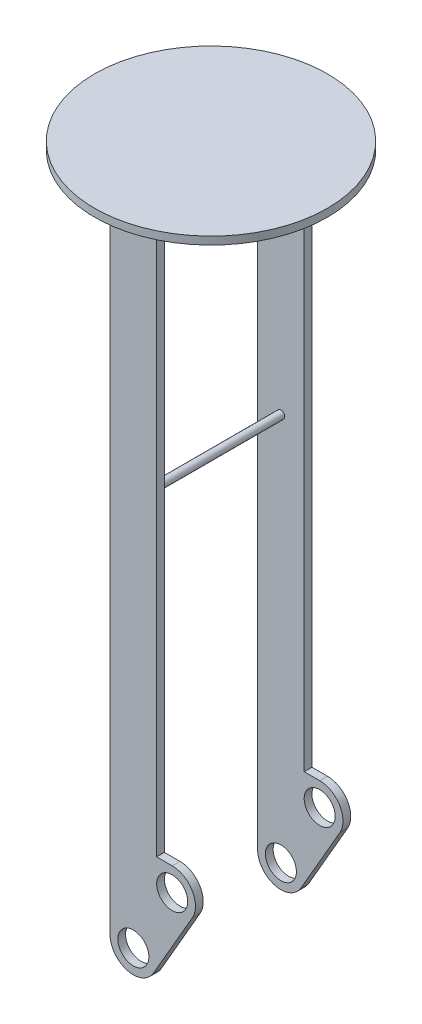
SolidWorks part; units mm, degrees
ref_plane "前视基准面" through (0, 0, 0) normal (0, 0, 1) x (1, 0, 0)
ref_plane "上视基准面" through (0, 0, 0) normal (0, 1, 0) x (1, 0, 0)
ref_plane "右视基准面" through (0, 0, 0) normal (1, 0, 0) x (0, 0, -1)
other "Configuration Table"
sketch "草图1" plane through (0, 0, 0) normal (0, 0, 1) x (1, 0, 0)
  line L0 (0, 0) -> (0, 518.4851) construction
  line L1 (-15, 500) -> (-15, 0)
  line L2 (15, 500) -> (15, 0)
  arc A0 (-15, 0) -> (15, 0) centre (0, 0) ccw
  arc A1 (15, 500) -> (-15, 500) centre (0, 500) ccw
  circle A2 centre (0, 500) radius 10
  circle A3 centre (0, 0) radius 10
  dimension "D1" = 30
  dimension "D2" = 30
  dimension "D4" = 20
  dimension "D5" = 20
  dimension "D3" = 500
extrude "凸台-拉伸1" add sketch "草图1" along normal blind 100 contours L0 A2 | A2 L0 | A3 | L2 A0 L1 A1 region at (-4.2441, 500, 0) region at (4.2441, 500, 0) region at (6.8711, 6.8711, 0)
sketch "草图2" plane through (0, 0, 100) normal (0, 0, 1) x (1, 0, 0)
  line L0 (15, 58.3013) -> (25, 58.3013)
  line L1 (15, 500) -> (15, 0) construction
  line L2 (37.9904, 35.8013) -> (12.9904, -7.5)
  line L3 (0, 0) -> (25, 43.3013) construction
  line L4 (15, 58.3013) -> (-15, 58.3013)
  line L5 (-15, 500) -> (-15, 0) construction
  line L6 (-15, 58.3013) -> (-15, 0)
  arc A0 (-15, 0) -> (15, 0) centre (0, 0) ccw construction
  arc A1 (-15, 0) -> (12.9904, -7.5) centre (0, 0) ccw
  circle A2 centre (25, 43.3013) radius 10
  arc A3 (37.9904, 35.8013) -> (25, 58.3013) centre (25, 43.3013) ccw
  circle A4 centre (0, 0) radius 10 construction
  circle A5 centre (0, 0) radius 10
  dimension "D2" = 20
  dimension "D1" = 60
  dimension "D3" = 50
extrude "凸台-拉伸2" add sketch "草图2" against normal up to surface (100 mm away) up to face at (0, 250, 0)
sketch "草图3" plane through (-15, 0, 0) normal (-1, 0, 0) x (0, 0, 1)
  line L0 (50, 525.1217) -> (50, -45.5346) construction
  line L1 (100, 500) -> (100, 0) construction
  line L2 (0, 500) -> (0, 0) construction
  line L3 (100, 0) -> (0, 0) construction
  line L4 (5, 400) -> (95, 400)
  line L5 (5, 400) -> (5, -40)
  line L6 (5, -40) -> (95, -40)
  line L7 (95, 400) -> (95, -40)
  dimension "D1" = 90
  dimension "D2" = 40
  dimension "D3" = 400
extrude "切除-拉伸1" cut sketch "草图3" against normal blind 122
sketch "草图4" plane through (0, 0, 0) normal (1, 0, 0) x (0, 0, -1)
  line L0 (-124.8476, 500) -> (76.1069, 500) construction
  dimension "D1" = 500
sketch "草图5" plane through (0, 0, 100) normal (0, 0, 1) x (1, 0, 0)
  line L0 (0, 250) -> (0, 0) construction
  circle A0 centre (0, 250) radius 2.5
  dimension "D1" = 5
  dimension "D2" = 250
extrude "凸台-拉伸3" add sketch "草图5" along direction (0, 0, 1) on the side against the normal up to surface (100 mm away) contours A0 region at (0, 250, 100) up to face at (11.3712, 164.7021, 0)
sketch "草图6" plane through (15, 0, 0) normal (1, 0, 0) x (0, 0, -1)
  line L0 (-124.8476, 500) -> (76.1069, 500) construction
  line L1 (-146.5509, 555.0847) -> (44.6261, 555.0847)
  line L2 (-146.5509, 555.0847) -> (-146.5509, 420)
  line L3 (-146.5509, 420) -> (44.6261, 420)
  line L4 (44.6261, 555.0847) -> (44.6261, 420)
  dimension "D1" = 80
extrude "切除-拉伸2" cut sketch "草图6" against normal blind 84
sketch "草图7" plane through (0, 420, 0) normal (0, 1, 0) x (1, 0, 0)
  line L0 (-58.3743, -50) -> (49.1225, -50) construction
  line L1 (-15, -100) -> (15, -100) construction
  line L2 (-15, 0) -> (15, 0) construction
  line L4 (0, 0) -> (0, -183.5249) construction
  circle A0 centre (0, -50) radius 75
  point P8 (0, 0)
  dimension "D1" = 150
extrude "凸台-拉伸4" add sketch "草图7" along normal blind 5 contours A0
